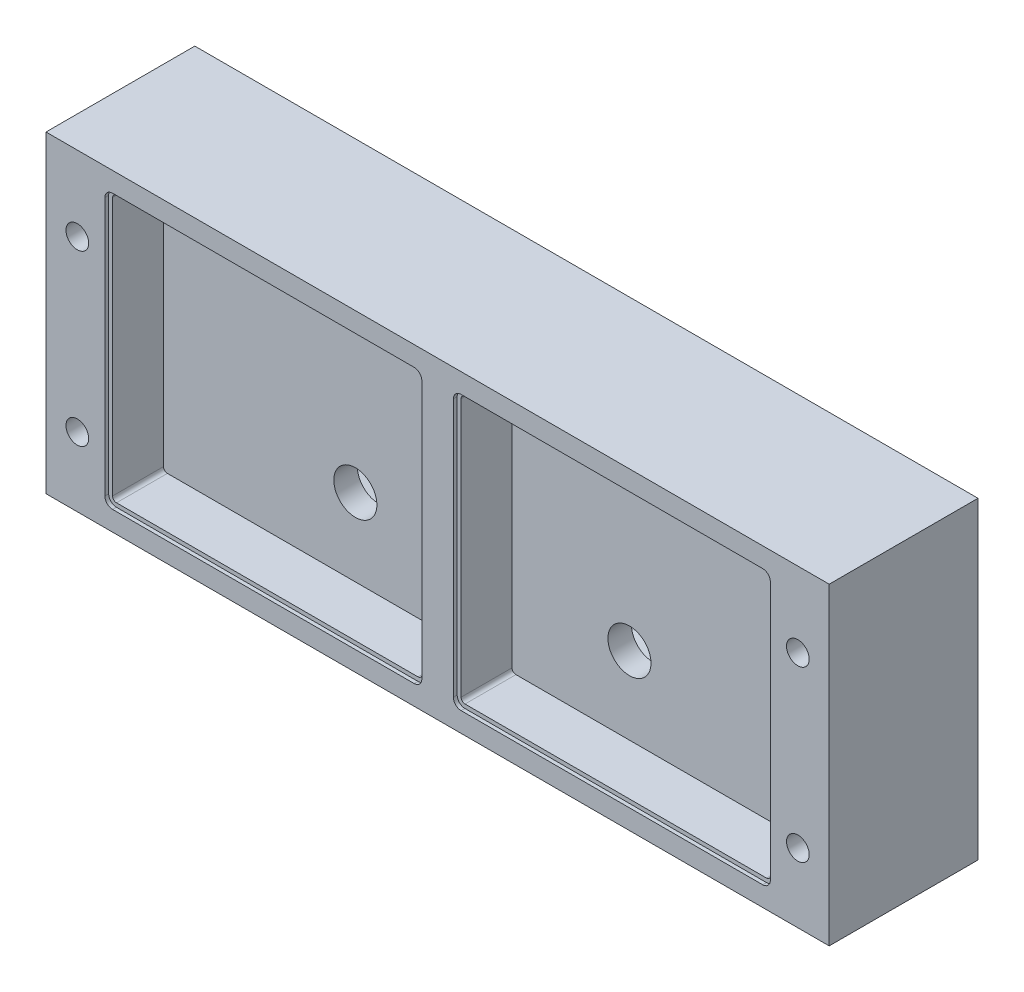
SolidWorks part; units mm, degrees
ref_plane "Front Plane" through (0, 0, 0) normal (0, 0, 1) x (1, 0, 0)
ref_plane "Top Plane" through (0, 0, 0) normal (0, 1, 0) x (1, 0, 0)
ref_plane "Right Plane" through (0, 0, 0) normal (1, 0, 0) x (0, 0, -1)
sketch "Sketch1" plane through (0, 0, 0) normal (0, 0, 1) x (1, 0, 0)
  line L1 (-33.75, 21.5625) -> (66.25, 21.5625)
  line L2 (-33.75, 21.5625) -> (-33.75, -18.4375)
  line L3 (-33.75, -18.4375) -> (66.25, -18.4375)
  line L4 (66.25, 21.5625) -> (66.25, -18.4375)
  dimension "D1" = 100
  dimension "D2" = 40
extrude "Boss-Extrude1" add sketch "Sketch1" along normal blind 38
sketch "Sketch2" plane through (0, 0, 0) normal (0, 0, -1) x (-1, 0, 0)
  line L0 (-66.25, -18.4375) -> (-66.25, 21.5625) construction
  line L1 (-58.25, 18.5625) -> (-18.75, 18.5625)
  line L2 (-58.25, 18.5625) -> (-58.25, -15.4375)
  line L3 (-58.25, -15.4375) -> (-18.75, -15.4375)
  line L4 (-18.75, 18.5625) -> (-18.75, -15.4375)
  line L5 (-13.75, 18.5625) -> (25.75, 18.5625)
  line L6 (-13.75, 18.5625) -> (-13.75, -15.4375)
  line L7 (-13.75, -15.4375) -> (25.75, -15.4375)
  line L8 (25.75, 18.5625) -> (25.75, -15.4375)
  line L9 (33.75, 21.5625) -> (33.75, -18.4375) construction
  line L10 (-66.25, 21.5625) -> (33.75, 21.5625) construction
  line L11 (33.75, -18.4375) -> (-66.25, -18.4375) construction
  dimension "D1" = 8
  dimension "D2" = 8
  dimension "D3" = 5
  dimension "D4" = 3
  dimension "D5" = 3
  dimension "D6" = 3
  dimension "D7" = 3
  dimension "D8" = 39.5
  dimension "D9" = 39.5
extrude "Cut-Extrude2" cut sketch "Sketch2" against normal blind 21 from offset 12 offset against normal yes
sketch "Sketch4" plane through (0, 0, 0) normal (0, 0, -1) x (-1, 0, 0)
  line L0 (-66.25, -18.4375) -> (-66.25, 21.5625) construction
  line L1 (33.75, 21.5625) -> (33.75, -18.4375) construction
  circle A0 centre (-62.25, 11.9848) radius 1.45
  circle A1 centre (-62.25, -9.6166) radius 1.45
  circle A2 centre (29.75, 11.9848) radius 1.45
  circle A3 centre (29.75, -9.6166) radius 1.45
  dimension "D1" = 4
  dimension "D2" = 4
extrude "Cut-Extrude4" cut sketch "Sketch4" against normal up to next
sketch "Sketch6" plane through (0, 21.5625, 0) normal (0, 1, 0) x (1, 0, 0)
  line L0 (-33.75, -38) -> (-33.75, 0) construction
  line L1 (66.25, -38) -> (-33.75, -38)
  line L2 (66.25, -38) -> (66.25, -19)
  line L3 (66.25, -19) -> (-33.75, -19)
  line L4 (-33.75, -38) -> (-33.75, -19)
extrude "Cut-Extrude5" cut sketch "Sketch6" against normal through all
fillet "Fillet1" radius 0.5 8 edges at (58.25, 18.5625, 15.5) (58.25, -15.4375, 15.5) (18.75, -15.4375, 15.5) (18.75, 18.5625, 15.5) (13.75, 18.5625, 15.5) (13.75, -15.4375, 15.5) (-25.75, -15.4375, 15.5) (-25.75, 18.5625, 15.5)
sketch "Sketch10" plane through (0, 0, 12) normal (0, 0, 1) x (1, 0, 0)
  line L8 (14.25, -14.9375) -> (14.25, 18.0625)
  line L9 (13.25, 19.0625) -> (-25.25, 19.0625)
  line L10 (-26.25, 18.0625) -> (-26.25, -14.9375)
  line L11 (-25.25, -15.9375) -> (13.25, -15.9375)
  line L12 (14.25, -14.9375) -> (14.25, 18.0625)
  line L13 (13.25, 19.0625) -> (-25.25, 19.0625)
  line L14 (-26.25, 18.0625) -> (-26.25, -14.9375)
  line L15 (-25.25, -15.9375) -> (13.25, -15.9375)
  arc A8 (14.25, 18.0625) -> (13.25, 19.0625) centre (13.25, 18.0625) ccw
  arc A9 (-25.25, 19.0625) -> (-26.25, 18.0625) centre (-25.25, 18.0625) ccw
  arc A10 (-26.25, -14.9375) -> (-25.25, -15.9375) centre (-25.25, -14.9375) ccw
  arc A11 (13.25, -15.9375) -> (14.25, -14.9375) centre (13.25, -14.9375) ccw
  arc A12 (14.25, 18.0625) -> (13.25, 19.0625) centre (13.25, 18.0625) ccw
  arc A13 (-25.25, 19.0625) -> (-26.25, 18.0625) centre (-25.25, 18.0625) ccw
  arc A14 (-26.25, -14.9375) -> (-25.25, -15.9375) centre (-25.25, -14.9375) ccw
  arc A15 (13.25, -15.9375) -> (14.25, -14.9375) centre (13.25, -14.9375) ccw
  dimension "D1" = 0.5
extrude "Cut-Extrude6" cut sketch "Sketch10" along normal blind 0.5 draft 2 from offset 6.5
sketch "Sketch11" plane through (0, 0, 12) normal (0, 0, 1) x (1, 0, 0)
  line L8 (58.75, -14.9375) -> (58.75, 18.0625)
  line L9 (57.75, 19.0625) -> (19.25, 19.0625)
  line L10 (18.25, 18.0625) -> (18.25, -14.9375)
  line L11 (19.25, -15.9375) -> (57.75, -15.9375)
  line L12 (58.75, -14.9375) -> (58.75, 18.0625)
  line L13 (57.75, 19.0625) -> (19.25, 19.0625)
  line L14 (18.25, 18.0625) -> (18.25, -14.9375)
  line L15 (19.25, -15.9375) -> (57.75, -15.9375)
  arc A8 (58.75, 18.0625) -> (57.75, 19.0625) centre (57.75, 18.0625) ccw
  arc A9 (19.25, 19.0625) -> (18.25, 18.0625) centre (19.25, 18.0625) ccw
  arc A10 (18.25, -14.9375) -> (19.25, -15.9375) centre (19.25, -14.9375) ccw
  arc A11 (57.75, -15.9375) -> (58.75, -14.9375) centre (57.75, -14.9375) ccw
  arc A12 (58.75, 18.0625) -> (57.75, 19.0625) centre (57.75, 18.0625) ccw
  arc A13 (19.25, 19.0625) -> (18.25, 18.0625) centre (19.25, 18.0625) ccw
  arc A14 (18.25, -14.9375) -> (19.25, -15.9375) centre (19.25, -14.9375) ccw
  arc A15 (57.75, -15.9375) -> (58.75, -14.9375) centre (57.75, -14.9375) ccw
  dimension "D1" = 0.5
extrude "Cut-Extrude7" cut sketch "Sketch11" along normal blind 0.5 draft 2 from offset 6.5
sketch "Sketch12" plane through (0, 0, 0) normal (0, 0, -1) x (-1, 0, 0)
  line L0 (-16.25, 21.5625) -> (-16.25, -22.3017) construction
  line L1 (-66.25, 21.5625) -> (33.75, 21.5625) construction
  line L2 (-66.25, -18.4375) -> (-66.25, 21.5625) construction
  line L3 (-66.25, -8.4375) -> (34.7654, -8.4375) construction
  line L4 (33.75, -18.4375) -> (-66.25, -18.4375) construction
  line L5 (-66.25, 7.0359) -> (33.75, 7.0359) construction
  line L6 (33.75, 21.5625) -> (33.75, -18.4375) construction
  line L7 (-16.25, 21.5625) -> (-16.25, 58.6816) construction
  arc A0 (-53.6512, 7.0359) -> (21.1512, 7.0359) centre (-16.25, 44.305) ccw construction
  arc A1 (-57.8659, 2.8361) -> (25.3659, 2.8361) centre (-16.25, 44.305) ccw
  arc A2 (-49.4365, 11.2357) -> (16.9365, 11.2357) centre (-16.25, 44.305) ccw
  arc A3 (-49.4365, 11.2357) -> (-57.8659, 2.8361) centre (-53.6512, 7.0359) ccw
  arc A4 (25.3659, 2.8361) -> (16.9365, 11.2357) centre (21.1512, 7.0359) ccw
  point P17 (-16.25, -8.495)
  dimension "D2" = 52.8
  dimension "D3" = 74.8024
  dimension "D1" = 10
  dimension "D4" = 22.7425
extrude "Cut-Extrude8" cut sketch "Sketch12" against normal blind 9
sketch "Sketch14" plane through (0, 0, 9) normal (0, 0, -1) x (-1, 0, 0)
  line L0 (-16.25, -8.5375) -> (-16.25, 44.2625) construction
  line L1 (-66.25, 21.5625) -> (33.75, 21.5625) construction
  line L2 (-66.25, -18.4375) -> (-66.25, 21.5625) construction
  circle A0 centre (-33.75, -5.5531) radius 2.75
  circle A1 centre (1.25, -5.5531) radius 2.75
  dimension "D4" = 52.8
  dimension "D6" = 17.5
  dimension "D7" = 17.5
  dimension "D1" = 22.7
  dimension "D2" = 50
  dimension "D3" = 52.8
  dimension "D5" = 52.8
extrude "Cut-Extrude9" cut sketch "Sketch14" against normal up to next
sketch "Sketch15" plane through (0, 0, 9) normal (0, 0, -1) x (-1, 0, 0)
  arc A4 (-49.4365, 11.2357) -> (-57.8659, 2.8361) centre (-53.6512, 7.0359) ccw
  arc A5 (-57.8659, 2.8361) -> (25.3659, 2.8361) centre (-16.25, 44.305) ccw
  arc A6 (25.3659, 2.8361) -> (16.9365, 11.2357) centre (21.1512, 7.0359) ccw
  arc A7 (-49.4365, 11.2357) -> (16.9365, 11.2357) centre (-16.25, 44.305) ccw
  arc A8 (-49.4365, 11.2357) -> (-57.8659, 2.8361) centre (-53.6512, 7.0359) ccw
  arc A9 (-57.8659, 2.8361) -> (25.3659, 2.8361) centre (-16.25, 44.305) ccw
  arc A10 (25.3659, 2.8361) -> (16.9365, 11.2357) centre (21.1512, 7.0359) ccw
  arc A11 (-49.4365, 11.2357) -> (16.9365, 11.2357) centre (-16.25, 44.305) ccw
  arc A16 (-50.1448, 10.5299) -> (-57.1576, 3.5419) centre (-53.6512, 7.0359) ccw
  arc A17 (-57.1576, 3.5419) -> (24.6576, 3.5419) centre (-16.25, 44.305) ccw
  arc A18 (24.6576, 3.5419) -> (17.6448, 10.5299) centre (21.1512, 7.0359) ccw
  arc A19 (-50.1448, 10.5299) -> (17.6448, 10.5299) centre (-16.25, 44.305) ccw
  dimension "D1" = 0
  dimension "D2" = 1
extrude "Boss-Extrude2" add sketch "Sketch15" along normal blind 1 draft 2 from offset 8
sketch "Sketch16" plane through (0, 0, 9) normal (0, 0, -1) x (-1, 0, 0)
  line L0 (-29.1543, -0.7327) -> (-29.4298, -1.694)
  line L1 (-3.3457, -0.7327) -> (-3.0702, -1.694)
  line L3 (1.4273, -10.6729) -> (1.7334, -11.6249)
  line L5 (-33.9273, -10.6729) -> (-34.2334, -11.6249)
  arc A0 (-29.4298, -1.694) -> (-3.0702, -1.694) centre (-16.25, 44.305) ccw
  arc A1 (-33.9273, -10.6729) -> (1.4273, -10.6729) centre (-16.25, 44.305) ccw
  arc A4 (-49.4365, 11.2357) -> (-57.8659, 2.8361) centre (-53.6512, 7.0359) ccw
  arc A5 (-57.8659, 2.8361) -> (25.3659, 2.8361) centre (-16.25, 44.305) ccw
  arc A6 (25.3659, 2.8361) -> (16.9365, 11.2357) centre (21.1512, 7.0359) ccw
  arc A7 (-49.4365, 11.2357) -> (16.9365, 11.2357) centre (-16.25, 44.305) ccw
  arc A9 (-34.2334, -11.6249) -> (1.7334, -11.6249) centre (-16.25, 44.305) ccw
  arc A11 (-29.1543, -0.7327) -> (-3.3457, -0.7327) centre (-16.25, 44.305) ccw
  dimension "D2" = 1
  dimension "D3" = 1
  dimension "D1" = 0
extrude "Cut-Extrude11" cut sketch "Sketch16" along normal blind 1 from offset 8
